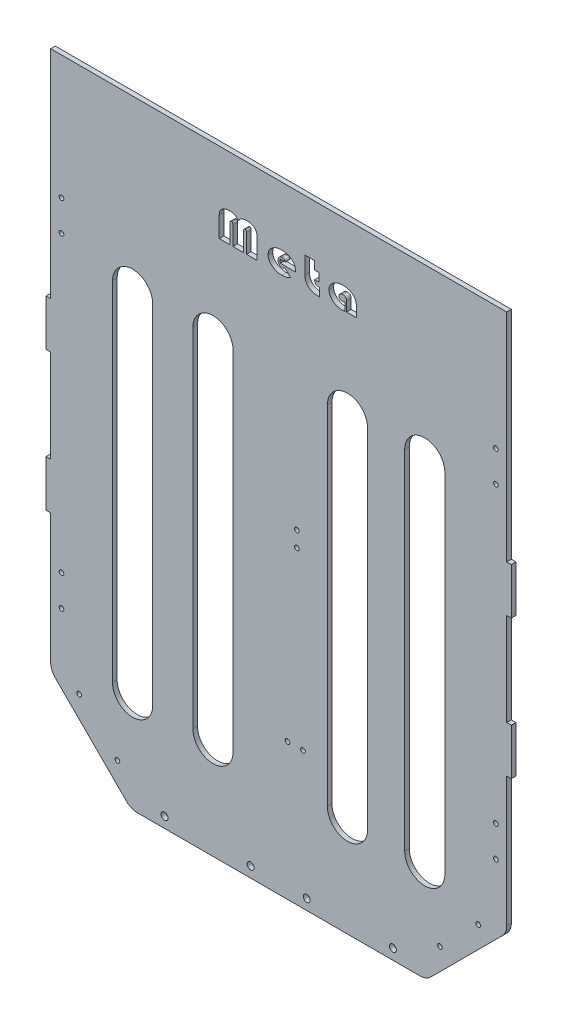
SolidWorks part; units mm, degrees
ref_plane "前视基准面" through (0, 0, 0) normal (0, 0, 1) x (1, 0, 0)
ref_plane "上视基准面" through (0, 0, 0) normal (0, 1, 0) x (1, 0, 0)
ref_plane "右视基准面" through (0, 0, 0) normal (1, 0, 0) x (0, 0, -1)
sketch "草图1" plane through (0, 0, 0) normal (0, 0, 1) x (1, 0, 0)
  line L0 (-147.5, 90) -> (-150.5, 90)
  line L1 (-147.5, 170) -> (147.5, 170)
  line L2 (-147.5, 170) -> (-147.5, 90)
  line L3 (-147.5, -170) -> (147.5, -170)
  line L4 (147.5, 170) -> (147.5, 90)
  line L5 (-147.5, 170) -> (147.5, -170) construction
  line L6 (-147.5, -170) -> (147.5, 170) construction
  line L7 (-150.5, 90) -> (-150.5, 60)
  line L8 (-150.5, 60) -> (-147.5, 60)
  line L9 (-147.5, 60) -> (-147.5, 0)
  line L10 (-147.5, 0) -> (-150.5, 0)
  line L11 (-150.5, 0) -> (-150.5, -30)
  line L12 (-150.5, -30) -> (-147.5, -30)
  line L13 (-147.5, -90) -> (-150.5, -90) construction
  line L14 (-150.5, -90) -> (-150.5, -120) construction
  line L15 (-150.5, -120) -> (-147.5, -120) construction
  line L16 (-147.5, -30) -> (-147.5, -90)
  line L17 (-147.5, -120) -> (-147.5, -170)
  line L18 (0, 0) -> (0, 121.9272) construction
  line L19 (147.5, -90) -> (150.5, -90) construction
  line L20 (150.5, -90) -> (150.5, -120) construction
  line L21 (150.5, -120) -> (147.5, -120) construction
  line L22 (147.5, 0) -> (150.5, 0)
  line L23 (150.5, 0) -> (150.5, -30)
  line L24 (150.5, -30) -> (147.5, -30)
  line L25 (147.5, 90) -> (150.5, 90)
  line L26 (150.5, 90) -> (150.5, 60)
  line L27 (150.5, 60) -> (147.5, 60)
  line L28 (147.5, -120) -> (147.5, -170)
  line L29 (147.5, -30) -> (147.5, -90)
  line L30 (147.5, 60) -> (147.5, 0)
  line L31 (-147.5, -90) -> (-147.5, -120)
  line L32 (147.5, -90) -> (147.5, -120)
  point P0 (0, 0)
  dimension "D1" = 295
  dimension "D2" = 340
  dimension "D3" = 30
  dimension "D4" = 3
  dimension "D5" = 80
  dimension "D6" = 3
  dimension "D7" = 30
  dimension "D8" = 30
  dimension "D9" = 3
  dimension "D10" = 50
  dimension "D11" = 60
extrude "凸台-拉伸1" add sketch "草图1" along normal blind 3
sketch "草图3" plane through (0, 0, 3) normal (0, 0, 1) x (1, 0, 0)
  line L0 (-147.5, -118) -> (-95.5, -170)
  line L1 (-147.5, -30) -> (-147.5, -170) construction
  line L2 (-147.5, -170) -> (147.5, -170) construction
  line L3 (-95.5, -170) -> (-147.5, -170)
  line L4 (-147.5, -170) -> (-147.5, -118)
  line L5 (147.5, -170) -> (147.5, -118)
  line L6 (147.5, -170) -> (147.5, -30) construction
  line L7 (147.5, -118) -> (95.5, -170)
  line L8 (95.5, -170) -> (147.5, -170)
  dimension "D1" = 52
  dimension "D2" = 52
  dimension "D3" = 52
  dimension "D4" = 52
extrude "切除-拉伸2" cut sketch "草图3" against normal through all
fillet "圆角1" [suppressed] radius 5
sketch "草图2" plane through (0, 0, 3) normal (0, 0, 1) x (1, 0, 0)
  line L0 (-95.5, -170) -> (95.5, -170) construction
  line L1 (0, -170) -> (0, -88.9982) construction
  circle A2 centre (73.85, -163.15) radius 2.25 construction
  circle A3 centre (18.15, -163.15) radius 2.25 construction
  circle A4 centre (-73.85, -163.15) radius 2.25 construction
  circle A5 centre (-18.15, -163.15) radius 2.25 construction
  circle A6 centre (11.8005, 40) radius 1.5
  circle A7 centre (11.8005, 30) radius 1.5
  circle A8 centre (73.85, -163.15) radius 2.25 construction
  circle A9 centre (18.15, -163.15) radius 2.25 construction
  circle A10 centre (-73.85, -163.15) radius 2.25 construction
  circle A11 centre (-18.15, -163.15) radius 2.25 construction
  circle A12 centre (-73.85, -163.15) radius 2.25
  circle A13 centre (-18.15, -163.15) radius 2.25
  circle A14 centre (18.15, -163.15) radius 2.25
  circle A15 centre (73.85, -163.15) radius 2.25
  dimension "D1" = 4.5
  dimension "D2" = 4.5
  dimension "D5" = 3
  dimension "D6" = 3
  dimension "D3" = 55.7
  dimension "D4" = 18.15
extrude "切除-拉伸1" cut sketch "草图2" against normal blind 10
sketch "草图4" plane through (0, 0, 3) normal (0, 0, 1) x (1, 0, 0)
  line L0 (147.5, 170) -> (-147.5, 170) construction
  line L1 (147.5, 90) -> (147.5, 170) construction
  line L2 (147.5, -118) -> (147.5, -30) construction
  line L3 (0, 170) -> (0, 113.7599) construction
  circle A0 centre (140.5, 150) radius 1.5
  circle A1 centre (140.5, 130) radius 1.5
  circle A2 centre (140.5, -60) radius 1.5
  circle A3 centre (140.5, -80) radius 1.5
  circle A4 centre (-140.5, -80) radius 1.5
  circle A5 centre (-140.5, -60) radius 1.5
  circle A6 centre (-140.5, 130) radius 1.5
  circle A7 centre (-140.5, 150) radius 1.5
  dimension "D1" = 20
  dimension "D2" = 20
  dimension "D3" = 190
  dimension "D4" = 20
  dimension "D5" = 7
  dimension "D6" = 7
  dimension "D7" = 7
  dimension "D8" = 7
  dimension "D9" = 3
  dimension "D10" = 3
  dimension "D11" = 3
  dimension "D12" = 3
extrude "切除-拉伸3" cut sketch "草图4" against normal through all
sketch "草图5" plane through (0, 0, 3) normal (0, 0, 1) x (1, 0, 0)
  line L0 (-94.5, 120) -> (-94.5, -105) construction
  line L1 (-81.5, 120) -> (-81.5, -105)
  line L2 (-107.5, 120) -> (-107.5, -105)
  line L3 (147.5, 170) -> (-147.5, 170) construction
  line L4 (-147.5, 60) -> (-147.5, 0) construction
  line L5 (-42.5, 120) -> (-42.5, -105) construction
  line L6 (-29.5, 120) -> (-29.5, -105)
  line L7 (-55.5, 120) -> (-55.5, -105)
  line L8 (44.5, 120) -> (44.5, -105) construction
  line L9 (57.5, 120) -> (57.5, -105)
  line L10 (31.5, 120) -> (31.5, -105)
  line L11 (94.5, 120) -> (94.5, -105) construction
  line L12 (107.5, 120) -> (107.5, -105)
  line L13 (81.5, 120) -> (81.5, -105)
  arc A0 (-81.5, 120) -> (-107.5, 120) centre (-94.5, 120) ccw
  arc A1 (-107.5, -105) -> (-81.5, -105) centre (-94.5, -105) ccw
  arc A2 (-29.5, 120) -> (-55.5, 120) centre (-42.5, 120) ccw
  arc A3 (-55.5, -105) -> (-29.5, -105) centre (-42.5, -105) ccw
  arc A4 (57.5, 120) -> (31.5, 120) centre (44.5, 120) ccw
  arc A5 (31.5, -105) -> (57.5, -105) centre (44.5, -105) ccw
  arc A6 (107.5, 120) -> (81.5, 120) centre (94.5, 120) ccw
  arc A7 (81.5, -105) -> (107.5, -105) centre (94.5, -105) ccw
  point P2 (-94.5, 7.5)
  point P14 (-42.5, 7.5)
  point P22 (44.5, 7.5)
  point P29 (94.5, 7.5)
  dimension "D1" = 13
  dimension "D2" = 225
  dimension "D3" = 50
  dimension "D4" = 53
  dimension "D8" = 52
  dimension "D9" = 87
  dimension "D5" = 2
  dimension "D6" = 2
  dimension "D7" = 2
extrude "切除-拉伸4" cut sketch "草图5" against normal through all
fillet "圆角3" radius 10 4 edges at (147.5, -118, 1.5) (95.5, -170, 1.5) (-95.5, -170, 1.5) (-147.5, -118, 1.5)
sketch "草图8" plane through (0, 0, 3) normal (0, 0, 1) x (1, 0, 0)
  line L0 (-129.0441, -122.3138) -> (-104.2954, -147.0625) construction
  line L1 (-98.4289, -167.0711) -> (-144.5711, -120.9289) construction
  line L2 (-147.5, -99.7493) -> (147.5, -99.7493) construction
  line L3 (-147.5, -30) -> (-147.5, -113.8579) construction
  line L4 (147.5, -113.8579) -> (147.5, -30) construction
  line L5 (0, -99.7493) -> (0, -54.3911) construction
  line L6 (129.0441, -122.3138) -> (104.2954, -147.0625) construction
  circle A0 centre (-129.0441, -122.3138) radius 1.5
  circle A1 centre (-104.2954, -147.0625) radius 1.5
  circle A2 centre (104.2954, -147.0625) radius 1.5
  circle A3 centre (129.0441, -122.3138) radius 1.5
  dimension "D1" = 3
  dimension "D2" = 3
  dimension "D3" = 10
  dimension "D4" = 35
extrude "切除-拉伸5" cut sketch "草图8" against normal through all
sketch "草图9" plane through (0, 0, 3) normal (0, 0, 1) x (1, 0, 0)
  line L1 (147.5, 170) -> (-147.5, 170)
  line L2 (147.5, 170) -> (147.5, 230)
  line L3 (147.5, 230) -> (-147.5, 230)
  line L4 (-147.5, 170) -> (-147.5, 230)
  dimension "D1" = 60
extrude "凸台-拉伸2" add sketch "草图9" against normal blind 3
sketch "草图10" plane through (0, 0, 0) normal (0, 0, -1) x (-1, 0, 0)
  circle A0 centre (-15.7145, -81.4977) radius 1.5
  circle A1 centre (-5.7145, -81.4977) radius 1.5
extrude "切除-拉伸6" cut sketch "草图10" against normal blind 10
sketch "草图12" plane through (0, 0, 3) normal (0, 0, 1) x (1, 0, 0)
  text T0 "Meta\r\n" font "华文琥珀" height in points 72
extrude "切除-拉伸7" cut sketch "草图12" against normal blind 10
